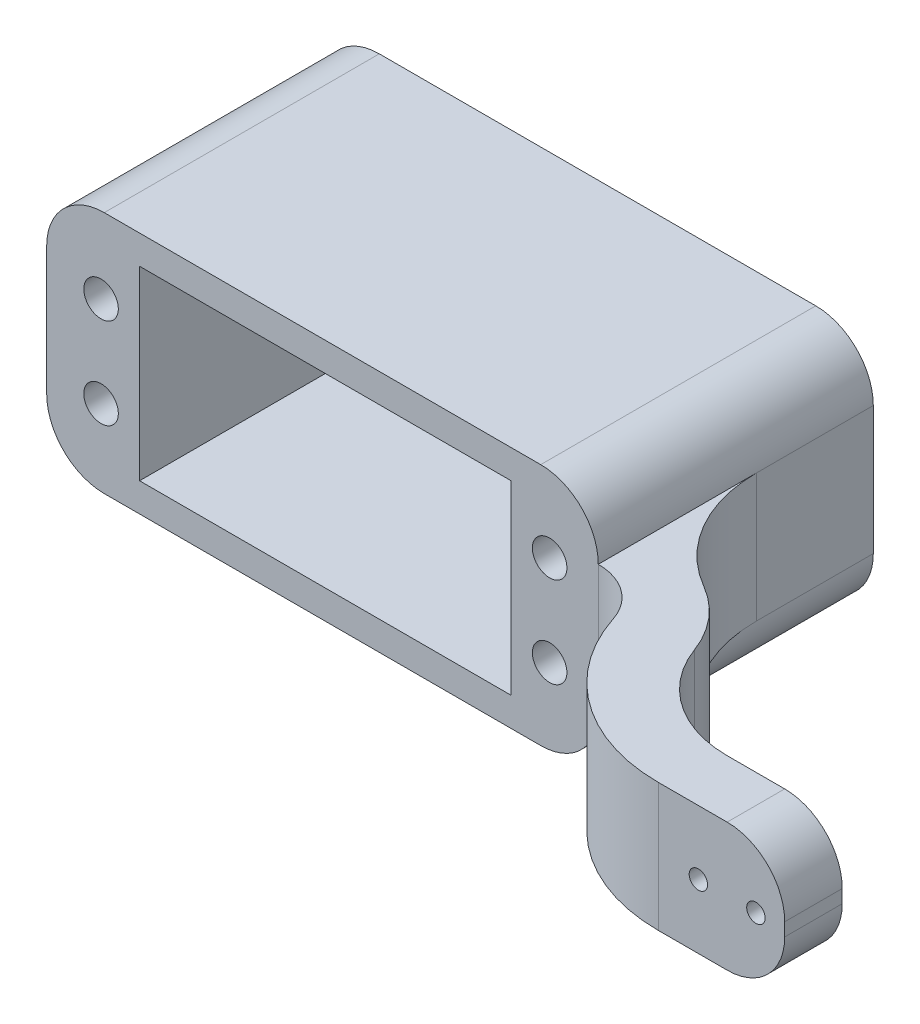
SolidWorks part; units mm, degrees
ref_plane "Front Plane" through (0, 0, 0) normal (0, 0, 1) x (1, 0, 0)
ref_plane "Top Plane" through (0, 0, 0) normal (0, 1, 0) x (1, 0, 0)
ref_plane "Right Plane" through (0, 0, 0) normal (1, 0, 0) x (0, 0, -1)
sketch "Sketch2" plane through (0, 0, 0) normal (0, 0, 1) x (1, 0, 0)
  line L0 (0, 10.25) -> (0, 5) construction
  line L1 (20.5, 10.25) -> (-20.5, 10.25) construction
  line L2 (20.5, 10.25) -> (20.5, -10.25) construction
  line L3 (20.5, -10.25) -> (-20.5, -10.25) construction
  line L4 (-20.5, 10.25) -> (-20.5, -10.25) construction
  line L5 (20.5, 10.25) -> (-20.5, -10.25) construction
  line L6 (20.5, -10.25) -> (-20.5, 10.25) construction
  line L7 (-24.75, 5) -> (24.75, 5) construction
  line L8 (-24.75, 5) -> (-24.75, -5) construction
  line L9 (-24.75, -5) -> (24.75, -5) construction
  line L10 (24.75, 5) -> (24.75, -5) construction
  line L11 (-24.75, 0) -> (-20.5, 0) construction
  line L12 (23.7659, 13.425) -> (-24.4, 13.425)
  line L13 (23.7659, -13.425) -> (-24.4, -13.425)
  line L14 (-30.75, 7.075) -> (-30.75, -7.075)
  line L15 (30.1159, -7.075) -> (30.1159, 7.075)
  circle A0 centre (-24.75, 5) radius 2.5 construction
  circle A1 centre (-24.75, -5) radius 2.5 construction
  circle A2 centre (24.75, 5) radius 2.5 construction
  circle A3 centre (24.75, -5) radius 2.5 construction
  arc A4 (-30.75, -7.075) -> (-24.4, -13.425) centre (-24.4, -7.075) ccw
  arc A5 (-24.4, 13.425) -> (-30.75, 7.075) centre (-24.4, 7.075) ccw
  arc A6 (23.7659, -13.425) -> (30.1159, -7.075) centre (23.7659, -7.075) ccw
  arc A7 (23.7659, 13.425) -> (30.1159, 7.075) centre (23.7659, 7.075) cw
  point P0 (0, 0)
  dimension "D7" = 5
  dimension "D9" = 6.35
  dimension "D1" = 20.5
  dimension "D2" = 41
  dimension "D3" = 49.5
  dimension "D4" = 10
  dimension "D5" = 3.175
  dimension "D6" = 3.175
  dimension "D8" = 6
extrude "Boss-Extrude1" add sketch "Sketch2" along normal mid plane 30.353
sketch "Sketch3" plane through (0, 0, 15.1765) normal (0, 0, 1) x (1, 0, 0)
  line L0 (-20.5, 10.25) -> (-20.5, -10.25)
  line L1 (-20.5, -10.25) -> (20.5, -10.25)
  line L2 (20.5, -10.25) -> (20.5, 10.25)
  line L3 (20.5, 10.25) -> (-20.5, 10.25)
extrude "Cut-Extrude1" cut sketch "Sketch3" against normal offset from surface (27.178 mm away) 3.175 up to face at (-0.3171, 0, -15.1765)
sketch "Sketch4" plane through (0, 0, 15.1765) normal (0, 0, 1) x (1, 0, 0)
  circle A0 centre (-24.75, 5) radius 1.905
  circle A1 centre (-24.75, -5) radius 1.905
  circle A2 centre (24.75, -5) radius 1.905
  circle A3 centre (24.75, 5) radius 1.905
  dimension "D1" = 3.81
extrude "Cut-Extrude2" cut sketch "Sketch4" against normal blind 12.7
sketch "Sketch5" plane through (-30.75, 0, 0) normal (-1, 0, 0) x (0, 0, 1)
  line L0 (-10.3505, -13.425) -> (-10.3505, 13.425) construction
  line L1 (-10.3505, 4.7625) -> (-4.0005, 4.7625)
  line L2 (-10.3505, 4.7625) -> (-10.3505, -4.7625)
  line L3 (-10.3505, -4.7625) -> (-4.0005, -4.7625)
  line L4 (-4.0005, 4.7625) -> (-4.0005, -4.7625)
  line L7 (15.1765, 13.425) -> (-15.1765, 13.425) construction
  line L8 (15.1765, -13.425) -> (-15.1765, -13.425) construction
  line L9 (-15.1765, 7.075) -> (-15.1765, -7.075) construction
  point P9 (-10.3505, 0)
  dimension "D1" = 9.525
  dimension "D2" = 6.35
  dimension "D3" = 4.826
extrude "Cut-Extrude3" cut sketch "Sketch5" against normal up to surface (10.25 mm away) up to face at (-20.5, 0, 1.5875)
sketch "Sketch7" plane through (0, 0, 15.1765) normal (0, 0, 1) x (1, 0, 0)
  line L0 (30.1159, 7.075) -> (30.1159, -7.075)
  line L1 (30.1159, 7.075) -> (68.2159, 7.075)
  line L3 (30.1159, -7.075) -> (68.2159, -7.075)
  line L4 (68.2159, 7.075) -> (68.2159, -7.075)
  line L5 (30.1159, 7.075) -> (28.6967, 7.075)
  line L6 (30.1159, 7.075) -> (30.1159, -7.075)
  line L7 (30.1159, -7.075) -> (28.6967, -7.075)
  line L8 (28.6967, 7.075) -> (28.6967, -7.075)
  line L9 (68.2159, 0) -> (28.6967, 0) construction
  circle A0 centre (65.0409, 0) radius 1.016
  circle A1 centre (58.6909, 0) radius 1.016
  line M17 (30.1159, -7.075) -> (30.1159, 7.075)
  dimension "D2" = 2.032
  dimension "D3" = 6.35
  dimension "D4" = 3.175
  dimension "D1" = 38.1
extrude "Boss-Extrude2" add sketch "Sketch7" along normal blind 17.526 and the other way blind 1.5875 separate body contours L4 L1 L3 M17 | L9 L4 L1 L6 A1 A0 region at (49.0112, 3.5753, 15.1765) region at (49.0112, -3.5753, 15.1765)
combine bodies "Combine1" operation type add bodies to combine 105 104
fillet "Fillet3" radius 15.875 1 edges at (30.1159, 0, 13.589)
fillet "Fillet4" radius 6.35 2 edges at (68.2159, -7.075, 23.1457) (68.2159, 7.075, 23.1457)
sketch "Sketch9" plane through (0, 7.075, 0) normal (0, 1, 0) x (1, 0, 0)
  line L1 (30.1159, -32.7025) -> (61.8659, -32.7025) construction
  line L2 (54.2646, -32.7025) -> (24.8898, -36.8503)
  line L3 (24.8898, -36.8503) -> (30.1159, -15.1765)
  line L4 (23.7659, -15.1765) -> (-24.4, -15.1765) construction
  line L5 (54.2646, -32.7025) -> (61.8659, -32.7025)
  line L7 (55.5159, -26.3525) -> (68.2159, -26.3525) construction
  line L10 (59.5029, -4.7266) -> (70.2622, -12.046)
  line L12 (68.2159, -13.589) -> (68.2159, -32.7025) construction
  line L13 (55.5159, -26.3525) -> (68.2159, -26.3525)
  line L14 (68.2159, -26.3525) -> (70.2622, -12.046)
  line L15 (59.5029, -4.7266) -> (42.7981, -7.2885)
  line L16 (42.7981, -7.2885) -> (38.0454, -11.4575)
  arc A0 (30.1159, -15.1765) -> (36.1531, -19.558) centre (30.1159, -21.5265) cw
  arc A1 (36.1531, -19.558) -> (54.2646, -32.7025) centre (54.2646, -13.6525) ccw
  arc A2 (38.0454, -11.4575) -> (43.6024, -18.0524) centre (31.6889, -22.4523) cw
  arc A3 (43.6024, -18.0524) -> (55.5159, -26.3525) centre (55.5159, -13.6525) ccw
  arc A4 (30.1159, 2.286) -> (45.9909, -13.589) centre (45.9909, 2.286) ccw construction
  arc A5 (30.1159, 2.286) -> (45.9909, -13.589) centre (45.9909, 2.286) ccw construction
  point P27 (0, 0)
  point P28 (0, 0)
  point P29 (39.8244, -13.2316)
  point P30 (63.3579, -5.814)
  point P31 (41.8632, -32.7025)
  point P32 (41.8632, -32.7025)
  point P33 (35.9895, -24.0279)
  point P34 (48.8772, -32.7025)
  point P35 (40.3774, -24.0279)
  point P36 (30.1159, -15.1765)
  point P37 (39.7103, -24.0279)
  point P38 (38.236, -22.7669)
  line M3 (30.1159, -32.7025) -> (61.8659, -32.7025)
  line M4 (61.8659, -32.7025) -> (61.8659, -13.589)
  line M5 (61.8659, -13.589) -> (45.9909, -13.589)
  line M8 (30.1159, -15.1765) -> (30.1159, -32.7025)
  dimension "D3" = 12.7
  dimension "D4" = 6.35
  dimension "D5" = 19.05
  dimension "D1" = 6.35
  dimension "D2" = 12.7
extrude "Cut-Extrude4" cut sketch "Sketch9" against normal through all contours A1 A0 M8 M3 | L3 L2 M3 M8 | A3 L10 M4 | A2 A3 M4 M5 region at (55.8608, 7.075, 15.7354) region at (35.8805, 7.075, 26.3311) region at (39.5261, 7.075, 34.4149)
